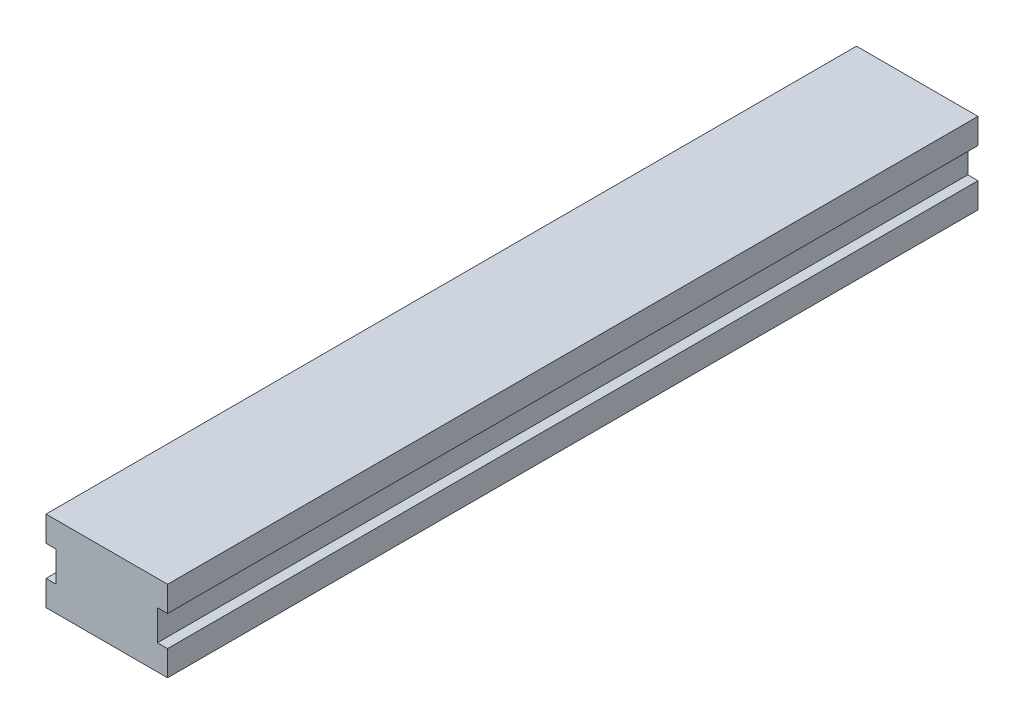
SolidWorks part; units mm, degrees
ref_plane "Front Plane" through (0, 0, 0) normal (0, 0, 1) x (1, 0, 0)
ref_plane "Top Plane" through (0, 0, 0) normal (0, 1, 0) x (1, 0, 0)
ref_plane "Right Plane" through (0, 0, 0) normal (1, 0, 0) x (0, 0, -1)
sketch "Sketch1" plane through (0, 0, 0) normal (0, 0, 1) x (1, 0, 0)
  line L0 (12, 8) -> (12, 5.5)
  line L1 (0, 0) -> (12, 0)
  line L3 (0, 8) -> (12, 8)
  line L4 (12, 5.5) -> (11, 5.5)
  line L5 (11, 5.5) -> (11, 2.5)
  line L6 (11, 2.5) -> (12, 2.5)
  line L7 (12, 2.5) -> (12, 0)
  line L8 (0, 8) -> (0, 5.5)
  line L9 (0, 5.5) -> (1, 5.5)
  line L10 (1, 5.5) -> (1, 2.5)
  line L11 (1, 2.5) -> (0, 2.5)
  line L12 (0, 2.5) -> (0, 0)
  dimension "D1" = 12
  dimension "D2" = 8
  dimension "D3" = 1
  dimension "D4" = 2.5
extrude "Boss-Extrude1" add sketch "Sketch1" along normal blind 80
